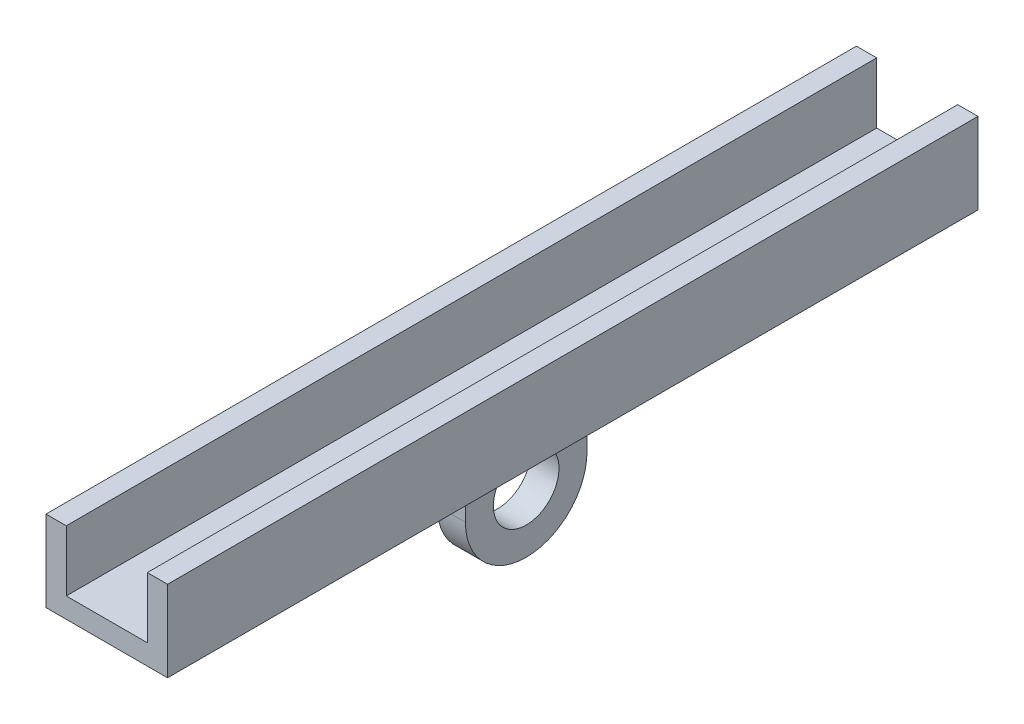
SolidWorks part; units mm, degrees
ref_plane "Front Plane" through (0, 0, 0) normal (0, 0, 1) x (1, 0, 0)
ref_plane "Top Plane" through (0, 0, 0) normal (0, 1, 0) x (1, 0, 0)
ref_plane "Right Plane" through (0, 0, 0) normal (1, 0, 0) x (0, 0, -1)
sketch "Sketch1" plane through (0, 0, 0) normal (0, 0, 1) x (1, 0, 0)
  line L0 (25, 20) -> (30, 20)
  line L1 (0, 0) -> (30, 0)
  line L2 (0, 0) -> (0, 20)
  line L3 (0, 20) -> (5, 20)
  line L4 (30, 0) -> (30, 20)
  line L6 (5, 20) -> (5, 5)
  line L7 (5, 5) -> (25, 5)
  line L8 (25, 20) -> (25, 5)
  dimension "D1" = 20
  dimension "D2" = 5
  dimension "D3" = 5
  dimension "D4" = 5
  dimension "D5" = 15
extrude "Boss-Extrude1" add sketch "Sketch1" along normal blind 200
sketch "Sketch2" plane through (30, 0, 0) normal (1, 0, 0) x (0, 0, -1)
  line L5 (-200, 0) -> (0, 0) construction
  line L6 (-115, -15) -> (-115, -10)
  line L7 (-85, -15) -> (-85, -10)
  line L10 (-125, 0) -> (-75, 0)
  circle A0 centre (-100, -15) radius 8.1
  arc A1 (-115, -15) -> (-85, -15) centre (-100, -15) ccw
  arc A2 (-85, -10) -> (-75, 0) centre (-75, -10) cw
  arc A3 (-115, -10) -> (-125, 0) centre (-125, -10) ccw
  point P4 (-100, 0)
  point P11 (-85, 0)
  point P14 (-115, 0)
  point P15 (-115, -12.6641)
  point P16 (-115, -10)
  dimension "D2" = 16.2
  dimension "D3" = 10
  dimension "D4" = 15
  dimension "D1" = 15
  dimension "D5" = 50
extrude "Boss-Extrude2" add sketch "Sketch2" against normal blind 7 from offset 11.5 offset against normal yes
